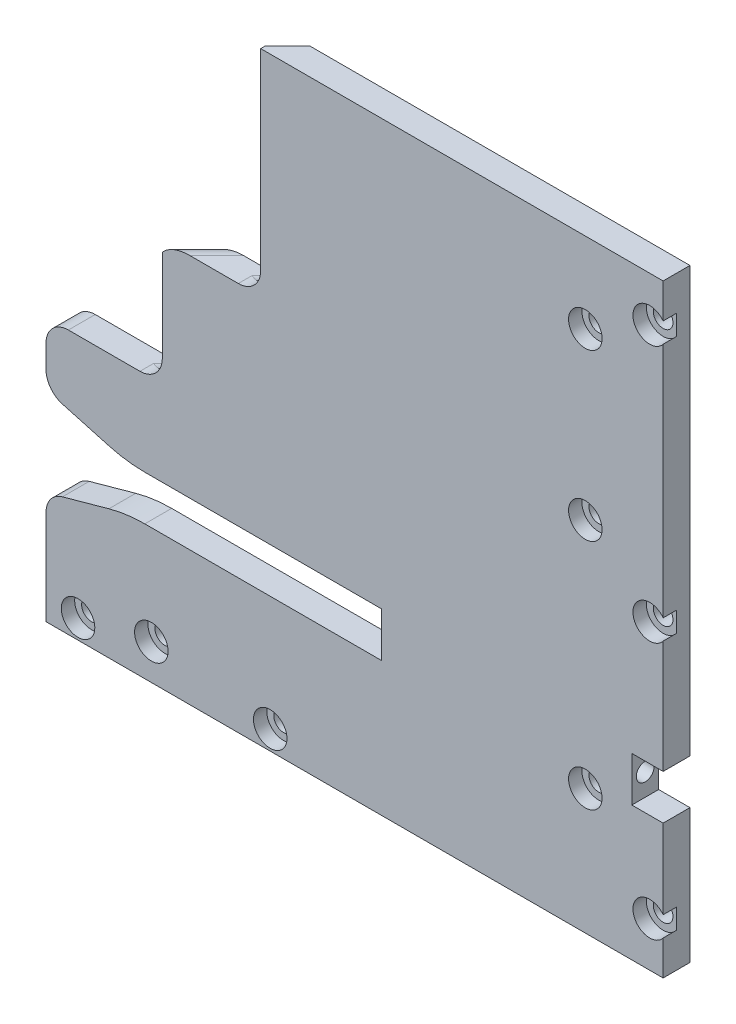
SolidWorks part; units mm, degrees
material "1060 Alloy"
ref_plane "Front Plane" through (0, 0, 0) normal (0, 0, 1) x (1, 0, 0)
ref_plane "Top Plane" through (0, 0, 0) normal (0, 1, 0) x (1, 0, 0)
ref_plane "Right Plane" through (0, 0, 0) normal (1, 0, 0) x (0, 0, -1)
sketch "Sketch1" plane through (0, 0, 0) normal (0, 0, 1) x (1, 0, 0)
  line L0 (0, 0) -> (-138, 0)
  line L1 (-138, 0) -> (-138, 30)
  line L2 (-138, 30) -> (-63, 30)
  line L3 (-63, 30) -> (-63, 40)
  line L4 (-63, 40) -> (-138, 40)
  line L5 (-138, 40) -> (-138, 59)
  line L6 (-138, 59) -> (-112, 59)
  line L7 (-112, 59) -> (-112, 87)
  line L8 (-112, 87) -> (-90, 87)
  line L9 (-90, 87) -> (-90, 135)
  line L10 (-90, 135) -> (0, 135)
  line L11 (0, 135) -> (0, 0)
  point P10 (-120, 40)
  point P14 (-120, 30)
  dimension "D1" = 30
  dimension "D2" = 138
  dimension "D3" = 75
  dimension "D4" = 10
  dimension "D5" = 19
  dimension "D6" = 26
  dimension "D7" = 28
  dimension "D8" = 135
  dimension "D9" = 22
  dimension "D10" = 18
extrude "Boss-Extrude1" add sketch "Sketch1" along normal blind 6
sketch "Sketch4" plane through (0, 0, 0) normal (0, 0, -1) x (-1, 0, 0)
  line L0 (120, 40) -> (138, 45)
  line L1 (138, 40) -> (138, 59) construction
  line L2 (138, 45) -> (138, 40)
  line L3 (138, 40) -> (120, 40)
  line L4 (120, 30) -> (138, 30)
  line L5 (138, 30) -> (138, 25)
  line L6 (138, 0) -> (138, 30) construction
  line L7 (138, 25) -> (120, 30)
  dimension "D1" = 5
  dimension "D2" = 5
extrude "Cut-Extrude1" cut sketch "Sketch4" against normal through all
sketch "Sketch5" plane through (-63, 0, 0) normal (-1, 0, 0) x (0, 0, 1)
  line L0 (6, 30) -> (0, 30) construction
  circle A0 centre (3, 35) radius 2
  point P5 (3, 30)
  dimension "D1" = 4
extrude "Cut-Extrude2" cut sketch "Sketch5" against normal through all
fillet "Fillet1" radius 30 2 edges at (-120, 40, 3) (-120, 30, 3)
chamfer "Chamfer1" distance 5 angle 45 2 edges at (-112, 73, 0) (-90, 111, 0)
fillet "Fillet2" radius 5 3 edges at (-138, 25, 3) (-138, 45, 3) (-138, 59, 3)
sketch "Sketch6" plane through (0, 0, 6) normal (0, 0, 1) x (1, 0, 0)
  line L0 (0, 0) -> (0, 135) construction
  line L1 (0, 40) -> (-7, 40)
  line L2 (0, 40) -> (0, 30)
  line L3 (0, 30) -> (-7, 30)
  line L4 (-7, 40) -> (-7, 30)
  line L5 (-115.9107, 40) -> (-63, 40) construction
  line L6 (-63, 30) -> (-115.9107, 30) construction
  dimension "D1" = 7
extrude "Cut-Extrude3" cut sketch "Sketch6" against normal through all
sketch "Sketch7" plane through (0, 0, 6) normal (0, 0, 1) x (1, 0, 0)
  line L3 (0, 40) -> (0, 135) construction
  line L4 (0, 135) -> (-90, 135) construction
  line L5 (-138, 0) -> (0, 0) construction
  point P1 (-3, 67.5)
  point P6 (-3, 10)
  point P7 (-3, 125)
  dimension "D1" = 3
  dimension "D2" = 10
  dimension "D3" = 67.5
  dimension "D4" = 10
sketch "Sketch9" plane through (0, 0, 6) normal (0, 0, 1) x (1, 0, 0)
  point P0 (-17.4, 117)
  point P1 (-17.4, 80)
  point P3 (-17.4, 28)
hole_wizard "Hole1" positions "Sketch10" profile "Sketch11" legacy end condition through all
sketch "Sketch10" plane through (0, 0, 6) normal (0, 0, 1) x (1, 0, 0)
  point P0 (-17.4, 117)
  point P3 (-17.4, 80)
  point P6 (-17.4, 28)
sketch "Sketch11" plane through (-17.4, 117, 6) normal (1, 0, 0) x (0, -1, 0)
  line L0 (0, 0) -> (0, 6)
  line L1 (0, 6) -> (2.2, 6)
  line L2 (2.2, 6) -> (2.2, 3)
  line L3 (2.2, 3) -> (3.75, 3)
  line L4 (3.75, 3) -> (3.75, 0)
  line L5 (3.75, 0) -> (0, 0)
  line L6 (0, 110) -> (0, -10) construction
  dimension "Diameter" = 4.4
  dimension "Depth" = 6
  dimension "C-Bore Diameter" = 7.5
  dimension "C-Bore Depth" = 3
hole_wizard "Hole2" positions "Sketch12" profile "Sketch13" legacy end condition through all
sketch "Sketch12" plane through (0, 0, 6) normal (0, 0, 1) x (1, 0, 0)
  point P0 (-3, 125)
  point P3 (-3, 67.5)
  point P6 (-3, 10)
sketch "Sketch13" plane through (-3, 125, 6) normal (1, 0, 0) x (0, -1, 0)
  line L0 (0, 0) -> (0, 6)
  line L1 (0, 6) -> (2.2, 6)
  line L2 (2.2, 6) -> (2.2, 3)
  line L3 (2.2, 3) -> (3.75, 3)
  line L4 (3.75, 3) -> (3.75, 0)
  line L5 (3.75, 0) -> (0, 0)
  line L6 (0, 110) -> (0, -10) construction
  dimension "Diameter" = 4.4
  dimension "Depth" = 6
  dimension "C-Bore Diameter" = 7.5
  dimension "C-Bore Depth" = 3
fillet "Fillet3" radius 5 4 edges at (-112, 59, 5.5) (-109.5, 59, 2.5) (-90, 87, 5.5) (-87.5, 87, 2.5)
fillet "Fillet5" radius 5 1 edges at (-109.5, 87, 2.5)
hole_wizard "Hole3" positions "Sketch14" profile "Sketch15" legacy end condition through all
sketch "Sketch14" plane through (0, 0, 6) normal (0, 0, 1) x (1, 0, 0)
  point P0 (-130.845, 4.2936)
  point P3 (-114.4514, 7.9069)
  point P6 (-87.8704, 4.2936)
sketch "Sketch15" plane through (-130.845, 4.2936, 6) normal (1, 0, 0) x (0, -1, 0)
  line L0 (0, 0) -> (0, 6)
  line L1 (0, 6) -> (2.2, 6)
  line L2 (2.2, 6) -> (2.2, 3)
  line L3 (2.2, 3) -> (3.75, 3)
  line L4 (3.75, 3) -> (3.75, 0)
  line L5 (3.75, 0) -> (0, 0)
  line L6 (0, 110) -> (0, -10) construction
  dimension "Diameter" = 4.4
  dimension "Depth" = 6
  dimension "C-Bore Diameter" = 7.5
  dimension "C-Bore Depth" = 3
